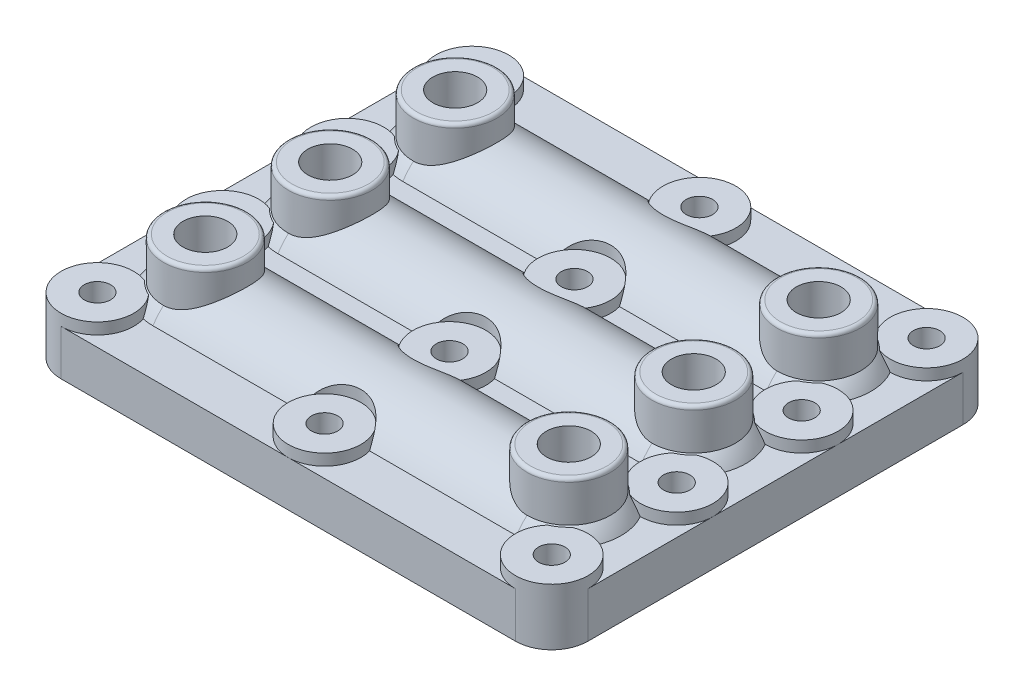
SolidWorks part; units mm, degrees
ref_plane "Front" through (0, 0, 0) normal (0, 0, 1) x (1, 0, 0)
ref_plane "Top" through (0, 0, 0) normal (0, 1, 0) x (1, 0, 0)
ref_plane "Right" through (0, 0, 0) normal (1, 0, 0) x (0, 0, -1)
sketch "Hole Layout" plane through (0, 0, 0) normal (0, 1, 0) x (1, 0, 0)
  line L0 (-31.75, 8.7312) -> (31.75, 8.7312) construction
  line L1 (0, 26.1937) -> (0, -26.1937) construction
  line L2 (-31.75, 26.1937) -> (31.75, 26.1937) construction
  line L3 (-31.75, -8.7313) -> (31.75, -8.7312) construction
  line L4 (-31.75, -26.1937) -> (31.75, -26.1937) construction
  circle A0 centre (-31.75, 26.1937) radius 3.175
  circle A1 centre (0, 26.1937) radius 3.175
  circle A2 centre (31.75, 26.1937) radius 3.175
  circle A3 centre (-31.75, 8.7312) radius 3.175
  circle A4 centre (0, 8.7312) radius 3.175
  circle A5 centre (31.75, 8.7312) radius 3.175
  circle A6 centre (-31.75, -8.7313) radius 3.175
  circle A7 centre (0, -8.7312) radius 3.175
  circle A8 centre (31.75, -8.7312) radius 3.175
  circle A9 centre (-31.75, -26.1937) radius 3.175
  circle A10 centre (0, -26.1937) radius 3.175
  circle A11 centre (31.75, -26.1937) radius 3.175
  circle A12 centre (-31.75, 26.1937) radius 2.413
  point P5 (0, 0)
  point P8 (0, 26.1937)
  point P10 (0, 8.7312)
  point P11 (0, -8.7312)
  dimension "D8" = 6.35
  dimension "D9" = 6.35
  dimension "D10" = 6.35
  dimension "D11" = 6.35
  dimension "D12" = 6.35
  dimension "D13" = 6.35
  dimension "D14" = 6.35
  dimension "D15" = 6.35
  dimension "D16" = 6.35
  dimension "D17" = 6.35
  dimension "D18" = 6.35
  dimension "D19" = 6.35
  dimension "D20" = 4.826
  dimension "D1" = 63.5
  dimension "D2" = 52.3875
  dimension "D3" = 63.5
  dimension "D4" = 8.7312
  dimension "D5" = 63.5
  dimension "D6" = 8.7312
  dimension "D7" = 63.5
sketch "Gas Layout" plane through (0, 0, 0) normal (0, 1, 0) x (1, 0, 0)
  line L0 (-25.4, 0) -> (25.4, 0) construction
  line L1 (-25.4, 17.4625) -> (25.4, 17.4625) construction
  line L2 (-25.4, -17.4625) -> (25.4, -17.4625) construction
  line L3 (0, 17.4625) -> (0, -17.4625) construction
  circle A0 centre (-25.4, 17.4625) radius 1.5875
  circle A1 centre (-25.4, 0) radius 1.5875
  circle A2 centre (-25.4, -17.4625) radius 1.5875
  circle A3 centre (25.4, 17.4625) radius 1.5875
  circle A4 centre (25.4, 0) radius 1.5875
  circle A5 centre (25.4, -17.4625) radius 1.5875
  point P5 (0, 17.4625)
  point P18 (0, 0)
  point P19 (0, -17.4625)
  dimension "D4" = 3.175
  dimension "D5" = 3.175
  dimension "D6" = 3.175
  dimension "D7" = 3.175
  dimension "D8" = 3.175
  dimension "D9" = 3.175
  dimension "D1" = 50.8
  dimension "D2" = 50.8
  dimension "D3" = 50.8
  dimension "D10" = 34.925
sketch "Gas Channel" plane through (0, 0, 0) normal (0, 1, 0) x (1, 0, 0)
  line L0 (-19.05, 17.4625) -> (19.05, 17.4625) construction
  line L1 (19.05, 15.2174) -> (19.05, 19.7076) construction
  line L2 (-25.4, 17.4625) -> (25.4, 17.4625) construction
  line L3 (-19.05, 19.7076) -> (19.05, 19.7076)
  line L4 (-19.05, 15.2174) -> (19.05, 15.2174)
  arc A0 (-19.05, 19.7076) -> (-19.05, 15.2174) centre (-19.05, 17.4625) ccw
  arc A1 (19.05, 15.2174) -> (19.05, 19.7076) centre (19.05, 17.4625) ccw
  point P5 (0, 17.4625)
  dimension "D1" = 19.05
  dimension "D2" = 4.4901
sketch "Perimeter" plane through (0, 0, 0) normal (0, 1, 0) x (1, 0, 0)
  line L0 (-31.75, 31.2737) -> (31.75, 31.2737)
  line L1 (-36.83, 26.1937) -> (-36.83, -26.1937)
  line L2 (36.83, 26.1937) -> (36.83, -26.1937)
  line L3 (-31.75, -31.2737) -> (31.75, -31.2737)
  circle A0 centre (-31.75, 26.1937) radius 5.08
  circle A1 centre (31.75, 26.1937) radius 5.08
  circle A2 centre (-31.75, -26.1937) radius 5.08
  circle A3 centre (31.75, -26.1937) radius 5.08
  dimension "D1" = 10.16
  dimension "D2" = 10.16
  dimension "D3" = 10.16
  dimension "D4" = 10.16
sketch "Footprint A" plane through (0, 0, 0) normal (0, 1, 0) x (1, 0, 0)
  line L0 (-31.75, 8.7312) -> (31.75, 8.7312) construction
  circle A0 centre (-31.75, 26.1937) radius 3.302
  circle A1 centre (0, 26.1937) radius 3.302
  circle A2 centre (31.75, 26.1937) radius 3.302
  circle A3 centre (-31.75, 8.7312) radius 3.302
  circle A4 centre (0, 8.7312) radius 3.302
  circle A5 centre (31.75, 8.7312) radius 3.302
  circle A6 centre (-31.75, -8.7313) radius 3.302
  circle A7 centre (0, -8.7312) radius 3.302
  circle A8 centre (31.75, -8.7312) radius 3.302
  circle A9 centre (-31.75, -26.1937) radius 3.302
  circle A10 centre (0, -26.1937) radius 3.302
  circle A11 centre (31.75, -26.1937) radius 3.302
  dimension "D1" = 6.604
  dimension "D2" = 6.604
  dimension "D3" = 6.604
  dimension "D4" = 6.604
  dimension "D5" = 6.604
  dimension "D6" = 6.604
  dimension "D7" = 6.604
  dimension "D8" = 6.604
  dimension "D9" = 6.604
  dimension "D10" = 6.604
  dimension "D11" = 6.604
  dimension "D12" = 6.604
sketch "Footprint B" plane through (0, 0, 0) normal (0, 1, 0) x (1, 0, 0)
  line L0 (-31.75, 31.2737) -> (31.75, 31.2737)
  line L1 (-36.83, 26.1937) -> (-36.83, -26.1937)
  line L2 (36.83, 26.1937) -> (36.83, -26.1937)
  line L3 (-31.75, -31.2737) -> (31.75, -31.2737)
  arc A0 (-31.75, 31.2737) -> (-36.83, 26.1937) centre (-31.75, 26.1937) ccw
  arc A6 (36.83, 26.1937) -> (31.75, 31.2737) centre (31.75, 26.1937) ccw
  arc A12 (-36.83, -26.1937) -> (-31.75, -31.2737) centre (-31.75, -26.1937) ccw
  arc A13 (31.75, -31.2737) -> (36.83, -26.1937) centre (31.75, -26.1937) ccw
  dimension "D1" = 10.16
  dimension "D2" = 10.16
  dimension "D3" = 10.16
  dimension "D4" = 5.08
extrude "Boss-Extrude1" add sketch "Footprint B" along normal blind 1.5875 contours L3 A13 L2 A6 L0 A0 L1 A12 region at (0, 0, 0)
ref_plane "Plane3" through (0, 1.5875, 0) normal (0, 1, 0) x (1, 0, 0)
sketch "Main Body A" plane through (0, 1.5875, 0) normal (0, 1, 0) x (1, 0, 0)
  line L0 (-36.83, 26.1937) -> (-36.83, -26.1938)
  line L1 (-31.75, -31.2738) -> (31.75, -31.2738)
  line L2 (36.83, -26.1938) -> (36.83, 26.1937)
  line L3 (31.75, 31.2737) -> (-31.75, 31.2737)
  line L4 (-31.75, 31.2737) -> (31.75, 31.2737) construction
  line L5 (-31.75, -31.2737) -> (31.75, -31.2737) construction
  line L6 (36.83, 26.1937) -> (36.83, -26.1937) construction
  line L7 (-36.83, 26.1937) -> (-36.83, -26.1937) construction
  arc A0 (-36.83, -26.1938) -> (-31.75, -31.2738) centre (-31.75, -26.1937) ccw
  arc A1 (31.75, -31.2738) -> (36.83, -26.1938) centre (31.75, -26.1937) ccw
  arc A2 (36.83, 26.1937) -> (31.75, 31.2737) centre (31.75, 26.1937) ccw
  arc A3 (-36.83, 26.1937) -> (-31.75, 31.2737) centre (-31.75, 26.1937) cw
  dimension "D1" = 5.08
extrude "Boss-Extrude2" add sketch "Main Body A" along normal blind 4.7625
sketch "Inlet/outlet posts" plane through (0, 0, 0) normal (0, 1, 0) x (1, 0, 0)
  circle A0 centre (25.4, 17.4625) radius 5.842
  circle A2 centre (25.4, 0) radius 5.842
  circle A3 centre (25.4, -17.4625) radius 5.842
  circle A4 centre (-25.4, -17.4625) radius 5.842
  circle A5 centre (-25.4, 0) radius 5.842
  circle A6 centre (-25.4, 17.4625) radius 5.842
  dimension "D1" = 11.684
  dimension "D2" = 11.684
  dimension "D3" = 11.684
  dimension "D4" = 11.684
  dimension "D5" = 11.684
  dimension "D6" = 11.684
extrude "Boss-Extrude4" add sketch "Inlet/outlet posts" along normal blind 13.7795
sketch "Sketch21" plane through (0, 1.5875, 0) normal (0, 1, 0) x (-1, 0, 0)
  line L0 (-41.0473, -17.4625) -> (41.0473, -17.4625) construction
  line L1 (0, -17.4625) -> (0, 0) construction
  line L2 (25.4, -17.4625) -> (-25.4, -17.4625) construction
  line L3 (25.4, -17.4625) -> (-25.4, -17.4625) construction
  line L5 (25.4, -8.7312) -> (-25.4, -8.7313)
  line L6 (34.1313, -17.4625) -> (-34.1313, -17.4625)
  arc A0 (34.1313, -17.4625) -> (25.4, -8.7312) centre (25.4, -17.4625) ccw
  arc A1 (-25.4, -8.7313) -> (-34.1313, -17.4625) centre (-25.4, -17.4625) ccw
  point P9 (0, -17.4625)
  point P12 (0, -17.4625)
  point P18 (0, -8.7312)
  point P19 (0, -8.7312)
revolve "Revolve2" add sketch "Sketch21" angle 180 about L0
pattern_linear "LPattern1" count 3 spacing 17.4625 along (0, 0, 1) of "Revolve2"
sketch "Sketch22" plane through (0, 6.35, 0) normal (0, 1, 0) x (1, 0, 0)
  circle A0 centre (-31.75, 26.1937) radius 5.08
  circle A1 centre (-31.75, 8.7312) radius 5.08
  circle A2 centre (-31.75, -8.7313) radius 5.08
  circle A3 centre (-31.75, -26.1937) radius 5.08
  circle A4 centre (0, -26.1938) radius 5.08
  circle A5 centre (0, -8.7312) radius 5.08
  circle A6 centre (0, 8.7312) radius 5.08
  circle A7 centre (0, 26.1937) radius 5.08
  circle A8 centre (31.75, 26.1937) radius 5.08
  circle A9 centre (31.75, 8.7312) radius 5.08
  circle A10 centre (31.75, -8.7312) radius 5.08
  circle A11 centre (31.75, -26.1937) radius 5.08
  dimension "D1" = 10.16
  dimension "D2" = 10.16
  dimension "D3" = 10.16
  dimension "D4" = 10.16
  dimension "D5" = 10.16
  dimension "D6" = 10.16
  dimension "D7" = 10.16
  dimension "D8" = 10.16
  dimension "D9" = 10.16
  dimension "D10" = 10.16
  dimension "D11" = 10.16
  dimension "D12" = 10.16
extrude "Boss-Extrude5" add sketch "Sketch22" along normal blind 1.5875
sketch "Sketch23" plane through (0, 7.9375, 0) normal (0, 1, 0) x (1, 0, 0)
  circle A0 centre (0, -26.1937) radius 5.08
  circle A1 centre (0, -8.7312) radius 5.08
  circle A2 centre (0, 8.7312) radius 5.08
  circle A3 centre (0, 26.1937) radius 5.08
  dimension "D1" = 10.16
  dimension "D2" = 10.16
  dimension "D3" = 10.16
  dimension "D4" = 10.16
extrude "Cut-Extrude3" cut sketch "Sketch23" along normal through all
sketch "Sketch24" plane through (0, 7.9375, 0) normal (0, 1, 0) x (1, 0, 0)
  circle A0 centre (-31.75, 26.1937) radius 1.8415
  circle A1 centre (-31.75, 8.7312) radius 1.8415
  circle A2 centre (-31.75, -8.7313) radius 1.8415
  circle A3 centre (-31.75, -26.1937) radius 1.8415
  circle A4 centre (0, 26.1937) radius 1.8415
  circle A5 centre (0, 8.7312) radius 1.8415
  circle A6 centre (0, -8.7313) radius 1.8415
  circle A7 centre (0, -26.1937) radius 1.8415
  circle A8 centre (31.75, 26.1937) radius 1.8415
  circle A9 centre (31.75, 8.7312) radius 1.8415
  circle A10 centre (31.75, -8.7312) radius 1.8415
  circle A11 centre (31.75, -26.1937) radius 1.8415
  dimension "D1" = 3.683
extrude "Cut-Extrude4" cut sketch "Sketch24" against normal through all
sketch "Sketch19" plane through (0, 13.7795, 0) normal (0, 1, 0) x (1, 0, 0)
  circle A0 centre (-25.4, 17.4625) radius 3.1242
  circle A1 centre (-25.4, 0) radius 3.1242
  circle A2 centre (-25.4, -17.4625) radius 3.1242
  circle A3 centre (25.4, 17.4625) radius 3.1242
  circle A4 centre (25.4, 0) radius 3.1242
  circle A5 centre (25.4, -17.4625) radius 3.1242
  dimension "D1" = 6.2484
  dimension "D2" = 6.2484
  dimension "D3" = 6.2484
  dimension "D4" = 6.2484
  dimension "D5" = 6.2484
  dimension "D6" = 6.2484
extrude "Cut-Extrude2" cut sketch "Sketch19" against normal blind 5.842
extrude "Cut-Extrude1" cut sketch "Gas Channel" along normal blind 0.9322 contours A1 L3 A0 L4
sketch "Sketch13" plane through (0, 0.9322, 0) normal (0, -1, 0) x (1, 0, 0)
  line L0 (-22.0111, -17.4625) -> (21.8692, -17.4625) construction
  line L1 (-25.4, -17.4625) -> (25.4, -17.4625) construction
  line L2 (-19.05, 0) -> (19.05, 0) construction
  line L3 (-19.05, 2.2451) -> (19.05, 2.2451)
  line L4 (-19.05, -2.2451) -> (19.05, -2.2451)
  line L5 (-19.05, -19.7076) -> (19.05, -19.7076) construction
  line L6 (-19.05, -19.7076) -> (19.05, -19.7076)
  line L7 (-21.2951, -17.4625) -> (21.2951, -17.4625)
  arc A0 (-19.05, 2.2451) -> (-19.05, -2.2451) centre (-19.05, 0) ccw
  arc A1 (19.05, -2.2451) -> (19.05, 2.2451) centre (19.05, 0) ccw
  arc A3 (19.05, -19.7076) -> (19.05, -15.2174) centre (19.05, -17.4625) ccw construction
  arc A4 (-19.05, -15.2174) -> (-19.05, -19.7076) centre (-19.05, -17.4625) ccw construction
  arc A5 (19.05, -19.7076) -> (21.2951, -17.4625) centre (19.05, -17.4625) ccw
  arc A6 (-21.2951, -17.4625) -> (-19.05, -19.7076) centre (-19.05, -17.4625) ccw
  point P6 (0, 0)
revolve "Cut-Revolve7" cut sketch "Sketch13" angle 180 about L0
ref_axis "Axis1" through (0, 0, -37.8212) along (0, 0, 1)
pattern_linear "LPattern6" count 3 spacing 17.4625 along (0, 0, 1) of "Cut-Extrude1", "Cut-Revolve7"
ref_plane "Plane1" through (19.05, 0, 0) normal (1, 0, 0) x (0, 0, -1)
sketch "Sketch14" plane through (19.05, 0, 0) normal (1, 0, 0) x (0, 0, -1)
  line L0 (26.1937, 0) -> (-26.1937, 0) construction
  line L3 (15.2174, 0.9322) -> (19.7076, 0.9322) construction
  line L4 (17.4625, -0.3456) -> (17.4625, 2.2099) construction
  line L5 (12.9152, 7.9375) -> (22.0672, 7.9375) construction
  circle A0 centre (17.4625, 1.5875) radius 1.5875
  point P8 (17.4625, 0.9322)
  point P9 (17.4625, 0.9322)
  dimension "D1" = 3.175
  dimension "D2" = 6.35
ref_plane "Plane2" through (0, 7.9375, 0) normal (0, 1, 0) x (1, 0, 0)
revolve "Cut-Revolve8" cut sketch "Sketch14" angle 90 about L5 reverse direction yes
pattern_linear "LPattern7" count 3 spacing 17.4625 along (0, 0, 1) of "Cut-Revolve8"
mirror "Mirror1" about plane through (0, 0, 0) normal (1, 0, 0) of "LPattern7"
fillet "Fillet1" radius 0.508 6 edges at (25.4, 13.7795, 23.3045) (-25.4, 13.7795, 23.3045) (-25.4, 13.7795, 5.842) (25.4, 13.7795, 5.842) (25.4, 13.7795, -11.6205) (-25.4, 13.7795, -11.6205)
sketch "Sketch25" plane through (0, 0, 0) normal (0, -1, 0) x (1, 0, 0)
  line L0 (-19.05, -15.2174) -> (19.05, -15.2174) construction
  line L1 (-19.05, -15.2174) -> (19.05, -15.2174)
  line L2 (0, -11.9062) -> (0, -15.2174) construction
  line L3 (0, -26.1937) -> (0, 26.1937) construction
  line L4 (-23.6729, -17.4625) -> (23.6729, -17.4625) construction
  line L5 (-25.4, -17.4625) -> (25.4, -17.4625) construction
  line L6 (-23.6729, -12.6728) -> (23.6729, -12.6728)
  line L7 (-23.6729, -22.2522) -> (23.6729, -22.2522)
  circle A0 centre (0, -8.7312) radius 3.175 construction
  arc A1 (-23.6729, -12.6728) -> (-23.6729, -22.2522) centre (-23.6729, -17.4625) ccw
  arc A2 (23.6729, -22.2522) -> (23.6729, -12.6728) centre (23.6729, -17.4625) ccw
  point P13 (0, -17.4625)
  point P19 (0, -13.5618)
  point P20 (0, -12.6728)
  dimension "D1" = 0.889
  dimension "D2" = 23.6729
  dimension "D3" = 4.7897
sketch "Sketch27" plane through (0, 0, 0) normal (1, 0, 0) x (0, 0, -1)
  line L1 (13.5618, -0.4987) -> (12.6728, -0.4987)
  line L2 (12.6728, -0.4987) -> (12.6728, 0.3903)
  line L3 (12.6728, 0) -> (12.6728, 2.8803) construction
  line L4 (26.1937, 0) -> (-26.1937, 0) construction
  arc A0 (13.5618, -0.4987) -> (12.6728, 0.3903) centre (13.5618, 0.3903) ccw
  dimension "D1" = 1.778
sweep "Cut-Sweep1" cut profiles "Sketch27" path "Sketch25"
pattern_linear "LPattern8" count 3 spacing 17.4625 along (0, 0, 1) of "Cut-Sweep1"
equation "\"SD\"= .25'Swage Footprint Diameter"
equation "\"D8@Hole Layout\" = \"SD\""
equation "\"D9@Hole Layout\" = \"SD\""
equation "\"D10@Hole Layout\" = \"SD\""
equation "\"D11@Hole Layout\" = \"SD\""
equation "\"D12@Hole Layout\" = \"SD\""
equation "\"D13@Hole Layout\" = \"SD\""
equation "\"D14@Hole Layout\" = \"SD\""
equation "\"D15@Hole Layout\" = \"SD\""
equation "\"D16@Hole Layout\" = \"SD\""
equation "\"D17@Hole Layout\" = \"SD\""
equation "\"D18@Hole Layout\" = \"SD\""
equation "\"D19@Hole Layout\" = \"SD\""
equation "\"Landing_1\" = .4'6-32 washer Landing Diameter"
equation "\"D1@Perimeter\"= \"Landing_1\""
equation "\"D2@Perimeter\"=\"Landing_1\""
equation "\"D3@Perimeter\"=\"Landing_1\""
equation "\"C_1\"= .01'Swage Clearance Diameter"
equation "\"D1@Footprint A\" = \"SD\" + \"C_1\""
equation "\"D2@Footprint A\" = \"SD\" + \"C_1\""
equation "\"D3@Footprint A\" = \"SD\" + \"C_1\""
equation "\"D4@Footprint A\" = \"SD\" + \"C_1\""
equation "\"D5@Footprint A\" = \"SD\" + \"C_1\""
equation "\"D6@Footprint A\" = \"SD\" + \"C_1\""
equation "\"D7@Footprint A\" = \"SD\" + \"C_1\""
equation "\"D8@Footprint A\" = \"SD\" + \"C_1\""
equation "\"D9@Footprint A\" = \"SD\" + \"C_1\""
equation "\"D10@Footprint A\" = \"SD\" + \"C_1\""
equation "\"D11@Footprint A\" = \"SD\" + \"C_1\""
equation "\"D12@Footprint A\"= \"SD\" + \"C_1\""
equation "\"D1@Main Body A\"= \"Landing_1\" / 2"
equation "\"OD\"= 1.55'O-Ring OD"
equation "\"W\"= .07'O-Ring Width"
equation "\"D2@Sketch25\"= \"OL\"/2 - 0.1886"
equation "\"OL\"= 2.23 / .995'Deformed O-Ring Long Dimension"
equation "\"D4@Perimeter\"=\"Landing_1\""
equation "\"D4@Footprint B\"=\"Landing_1\"/2"
equation "\"D3@Footprint B\"=\"Landing_1\""
equation "\"D2@Footprint B\"=\"Landing_1\""
equation "\"D1@Footprint B\"=\"Landing_1\""
equation "\"D1@Sketch22\"=\"Landing_1\""
equation "\"D2@Sketch22\"=\"Landing_1\""
equation "\"D3@Sketch22\"=\"Landing_1\""
equation "\"D4@Sketch22\"=\"Landing_1\""
equation "\"D5@Sketch22\"=\"Landing_1\""
equation "\"D6@Sketch22\"=\"Landing_1\""
equation "\"D7@Sketch22\"=\"Landing_1\""
equation "\"D8@Sketch22\"=\"Landing_1\""
equation "\"D9@Sketch22\"=\"Landing_1\""
equation "\"D10@Sketch22\"=\"Landing_1\""
equation "\"D11@Sketch22\"=\"Landing_1\""
equation "\"D12@Sketch22\"=\"Landing_1\""
equation "\"D1@Sketch23\"=\"Landing_1\""
equation "\"D2@Sketch23\"=\"Landing_1\""
equation "\"D3@Sketch23\"=\"Landing_1\""
equation "\"D4@Sketch23\"=\"Landing_1\""
